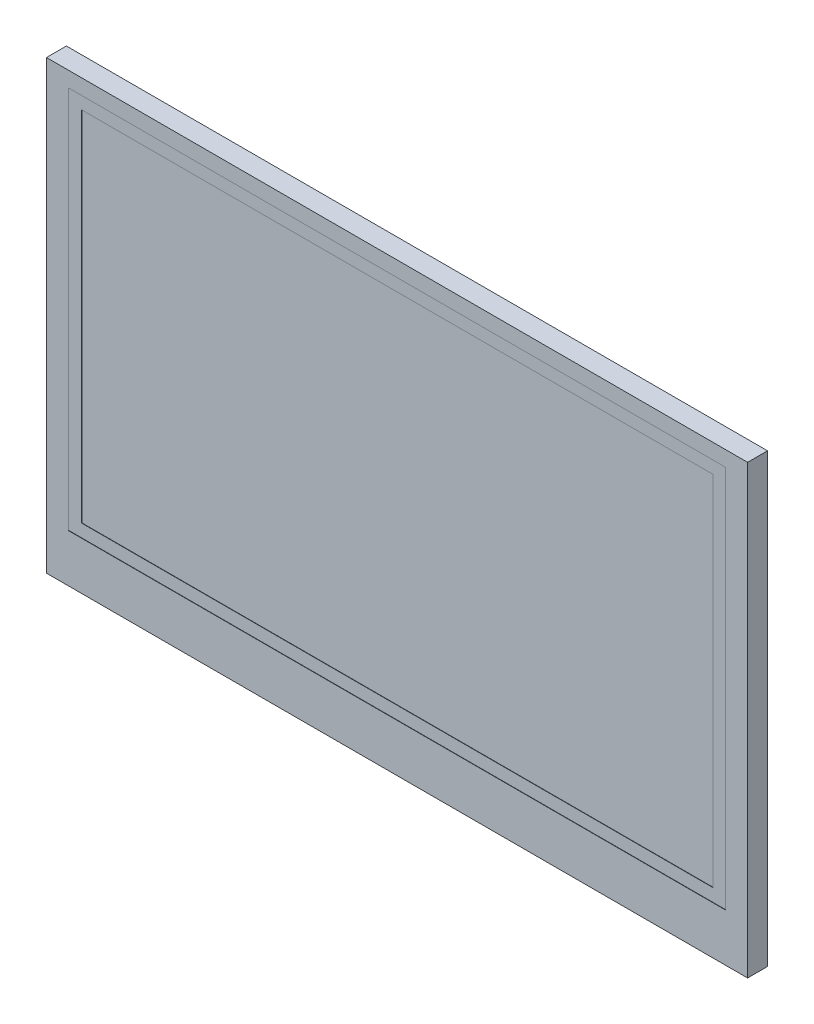
SolidWorks part; units mm, degrees
ref_plane "Front Plane" through (0, 0, 0) normal (0, 0, 1) x (1, 0, 0)
ref_plane "Top Plane" through (0, 0, 0) normal (0, 1, 0) x (1, 0, 0)
ref_plane "Right Plane" through (0, 0, 0) normal (1, 0, 0) x (0, 0, -1)
sketch "Sketch1" plane through (0, 0, 0) normal (0, 0, 1) x (1, 0, 0)
  line L1 (52.75, 33.6) -> (-52.75, 33.6)
  line L2 (52.75, 33.6) -> (52.75, -33.6)
  line L3 (52.75, -33.6) -> (-52.75, -33.6)
  line L4 (-52.75, 33.6) -> (-52.75, -33.6)
  line L5 (52.75, 33.6) -> (-52.75, -33.6) construction
  line L6 (52.75, -33.6) -> (-52.75, 33.6) construction
  line L7 (-49.45, 31.3) -> (49.45, 31.3)
  line L8 (-49.45, 31.3) -> (-49.45, -26.4)
  line L9 (-49.45, -26.4) -> (49.45, -26.4)
  line L10 (49.45, 31.3) -> (49.45, -26.4)
  line L11 (-47.52, 29.38) -> (47.52, 29.38)
  line L12 (-47.52, 29.38) -> (-47.52, -24.476)
  line L13 (-47.52, -24.476) -> (47.52, -24.476)
  line L14 (47.52, 29.38) -> (47.52, -24.476)
  point P0 (0, 0)
  dimension "D1" = 105.5
  dimension "D2" = 67.2
  dimension "D3" = 57.7
  dimension "D4" = 98.9
  dimension "D5" = 95.04
  dimension "D6" = 53.856
  dimension "D7" = 3.3
  dimension "D8" = 5.23
  dimension "D9" = 2.3
  dimension "D10" = 4.22
extrude "Boss-Extrude1" add sketch "Sketch1" along normal blind 3 contours L1 L4 L3 L2 L7 L10 L9 L8 region at (51.4992, 0, 0)
extrude "Boss-Extrude2" add sketch "Sketch1<3>" along normal blind 2.95 contours L10 L7 L8 L9 L11 L14 L13 L12 region at (0, 30.155, 0)
sketch "Sketch1<3>" plane through (0, 0, 0) normal (0, 0, 1) x (1, 0, 0) same geometry as "Sketch1"
extrude "Boss-Extrude3" add sketch "Sketch1<4>" along normal blind 2.9 contours L14 L11 L12 L13 region at (0, 2.452, 0)
sketch "Sketch1<4>" plane through (0, 0, 0) normal (0, 0, 1) x (1, 0, 0) same geometry as "Sketch1"
